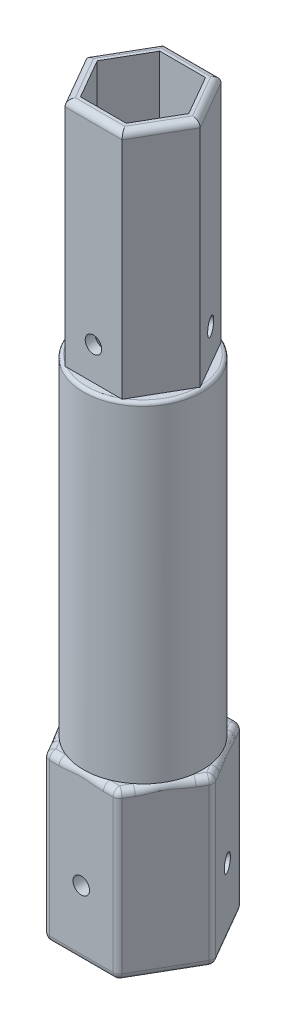
SolidWorks part; units mm, degrees
ref_plane "Front Plane" through (0, 0, 0) normal (0, 0, 1) x (1, 0, 0)
ref_plane "Top Plane" through (0, 0, 0) normal (0, 1, 0) x (1, 0, 0)
ref_plane "Right Plane" through (0, 0, 0) normal (1, 0, 0) x (0, 0, -1)
sketch "Sketch1" plane through (0, 0, 0) normal (0, 1, 0) x (1, 0, 0)
  line L1 (10.7965, 0) -> (5.3982, 9.35)
  line L2 (5.3982, 9.35) -> (-5.3982, 9.35)
  line L3 (-5.3982, 9.35) -> (-10.7965, 0)
  line L4 (-10.7965, 0) -> (-5.3982, -9.35)
  line L5 (-5.3982, -9.35) -> (5.3982, -9.35)
  line L6 (5.3982, -9.35) -> (10.7965, 0)
  circle A0 centre (0, 0) radius 9.35 construction
  dimension "D1" = 18.7
extrude "Base" add sketch "Sketch1" along normal blind 25 contours L6 L1 L2 L3 L4 L5
sketch "Sketch2" plane through (0, 25, 0) normal (0, 1, 0) x (1, 0, 0)
  circle A0 centre (0, 0) radius 9
  dimension "D1" = 18
extrude "Shaft" add sketch "Sketch2" along normal blind 50
sketch "Sketch3" plane through (0, 75, 0) normal (0, 1, 0) x (1, 0, 0)
  line L1 (8.6603, 0) -> (4.3301, 7.5)
  line L2 (4.3301, 7.5) -> (-4.3301, 7.5)
  line L3 (-4.3301, 7.5) -> (-8.6603, 0)
  line L4 (-8.6603, 0) -> (-4.3301, -7.5)
  line L5 (-4.3301, -7.5) -> (4.3301, -7.5)
  line L6 (4.3301, -7.5) -> (8.6603, 0)
  circle A0 centre (0, 0) radius 7.5 construction
  point P10 (0, 0)
  dimension "D1" = 15
extrude "MicMount" add sketch "Sketch3" along normal blind 35
sketch "Sketch4" plane through (0, 0, 0) normal (0, -1, 0) x (1, 0, 0)
  line L0 (5.3982, -9.35) -> (-5.3982, -9.35) construction
  line L1 (-3.6662, -6.35) -> (3.6662, -6.35)
  line L2 (3.6662, -6.35) -> (7.3323, 0)
  line L3 (7.3323, 0) -> (3.6662, 6.35)
  line L4 (3.6662, 6.35) -> (-3.6662, 6.35)
  line L5 (-3.6662, 6.35) -> (-7.3323, 0)
  line L6 (-7.3323, 0) -> (-3.6662, -6.35)
  circle A0 centre (0, 0) radius 6.35 construction
  dimension "D1" = 12.7
extrude "Cut-Extrude1" cut sketch "Sketch4" against normal up to surface (75 mm away) up to face at (0, 75, 0)
sketch "ScrewHoleLoc" plane through (6.4952, 0, -3.75) normal (0.866, 0, -0.5) x (-0.5, 0, -0.866)
  line L0 (0, 48.1931) -> (0, 111.8069) construction
  line L1 (9, 75) -> (-9, 75) construction
  point P0 (0, 80)
hole_wizard "ScrewHole" positions "3DSketch1" profile "Sketch6" hole size "Ø2.5" standard "ANSI Metric"
sketch3d "3DSketch1"
  point P0 (6.4952, 80, -3.75)
sketch "Sketch6" plane through (6.4952, 80, -3.75) normal (0, 1, 0) x (-0.5, 0, -0.866)
  line L0 (0, 0) -> (0, 2.7511)
  line L1 (0, 2.7511) -> (1.25, 2)
  line L2 (1.25, 2) -> (1.25, 0)
  line L5 (1.25, 0) -> (0, 0)
  line L10 (0, 2.7511) -> (-1.25, 2) construction
  line L11 (0, -6.35) -> (0, 107.95) construction
  dimension "Hole Dia." = 2.5
  dimension "Hole Depth" = 2
  dimension "Drill Angle" = 118
ref_axis "Axis1" through (0, 54.4687, 0) along (0, 1, 0)
pattern_circular "ScrewHoleS" count 3 over 360 about axis through (0, 54.4687, 0) along (0, 1, 0) of "ScrewHole"
sketch "Sketch7" plane through (0, 110, 0) normal (0, 1, 0) x (1, 0, 0)
  line L12 (3.4641, -6) -> (6.9282, 0)
  line L13 (6.9282, 0) -> (3.4641, 6)
  line L14 (3.4641, 6) -> (-3.4641, 6)
  line L15 (-3.4641, 6) -> (-6.9282, 0)
  line L16 (-6.9282, 0) -> (-3.4641, -6)
  line L17 (-3.4641, -6) -> (3.4641, -6)
  line L18 (3.4641, -6) -> (6.9282, 0)
  line L19 (6.9282, 0) -> (3.4641, 6)
  line L20 (3.4641, 6) -> (-3.4641, 6)
  line L21 (-3.4641, 6) -> (-6.9282, 0)
  line L22 (-6.9282, 0) -> (-3.4641, -6)
  line L23 (-3.4641, -6) -> (3.4641, -6)
  dimension "D1" = 1.5
extrude "Cut-Extrude2" cut sketch "Sketch7" against normal up to next
sketch "ShaftMountLoc" plane through (-8.0973, 0, -4.675) normal (-0.866, 0, -0.5) x (-0.5, 0, 0.866)
  line L0 (0, 10) -> (0, 7.4851) construction
  line L1 (5.3982, 25) -> (5.3982, 0) construction
  line L2 (-5.3982, 25) -> (-5.3982, 0) construction
  line L3 (-5.3982, 0) -> (5.3982, 0) construction
  point P0 (0, 10)
  dimension "D1" = 10
hole_wizard "ShaftMount" positions "3DSketch3" profile "Sketch10" hole size "Ø2.5" standard "ANSI Metric"
sketch3d "3DSketch3"
  point P0 (-8.0973, 10, -4.675)
sketch "Sketch10" plane through (-8.0973, 10, -4.675) normal (0, 1, 0) x (-0.5, 0, 0.866)
  line L0 (0, 0) -> (0, 18.7)
  line L1 (0, 18.7) -> (1.25, 18.7)
  line L2 (1.25, 18.7) -> (1.25, 0)
  line L5 (1.25, 0) -> (0, 0)
  line L11 (0, -6.35) -> (0, 107.95) construction
  dimension "Thru Hole Dia." = 2.5
  dimension "Thru Hole Depth" = 18.7
pattern_circular "CirPattern2" count 3 over 360 about axis through (0, 54.4687, 0) along (0, 1, 0) of "ShaftMount"
fillet "Fillet2" radius 1 24 edges at (8.0973, 0, -4.675) (-8.0973, 0, -4.675) (0, 0, 9.35) (5.4993, 0, 3.175) (0, 0, 6.35) (-5.4993, 0, 3.175) (-5.4993, 0, -3.175) (0, 0, -6.35) (5.4993, 0, -3.175) (5.3982, 12.5, 9.35) (8.0973, 25, 4.675) (10.7965, 12.5, 0) (8.0973, 0, 4.675) (-10.7965, 12.5, 0) (-8.0973, 25, 4.675) (-5.3982, 12.5, 9.35) (-8.0973, 0, 4.675) (5.3982, 12.5, -9.35) (0, 25, -9.35) (-5.3982, 12.5, -9.35) (0, 0, -9.35) (-8.0973, 25, -4.675) (8.0973, 25, -4.675) (0, 25, 9.35)
fillet "Fillet5" radius 1 6 edges at (6.4952, 110, -3.75) (6.4952, 110, 3.75) (0, 110, 7.5) (-6.4952, 110, 3.75) (-6.4952, 110, -3.75) (0, 110, -7.5)
fillet "Fillet8" radius 0.5 1 edges at (0, 75, 9)
equation "\"D1@Sketch3\"= \"SHAFT_MOUNTOD\""
equation "\"D1@Base\"=25"
equation "\"D1@Shaft\"=50"
equation "\"D1@Sketch2\"= \"SHAFT_D\""
equation "\"D1@Sketch4\" = \"SHAFT_BASEID\""
equation "\"D1@MicMount\" = \"SHAFT_MOUNTH\""
equation "\"D1@ShaftMountLoc\"= \"SHAFT_BASEHOLEH\""
equation "\"D1@Sketch1\" = \"SHAFT_BASEOD\""
equation "\"SHAFT_MOUNTOD\" = \"BMOUNT_HEXID\""
equation "\"CB_W\" = 5"
equation "\"CW_DEPTH\" = 1"
equation "\"PIN_SPACING\" = 2.54"
equation "\"PIN_D\" = 1"
equation "\"PCB_THICK\" = 1.5"
equation "\"TAP_HOLE\" = 2.5"
equation "\"SCREW_HOLE\" = 3"
equation "\"SLIPRING_D\" = 12.4"
equation "\"SLIPRING_MOUNTOD\" = 15"
equation "\"SLIPRING_MOUNTTHICK\" = 8"
equation "\"SLIPRING_MOUNT_LEGH\" = 12"
equation "\"PITCH_D\"= 44.45"
equation "\"HEX_D\"= 12.7"
equation "\"BODY_Y\"= 70"
equation "\"BODY_X\"= 60"
equation "\"BODY_Z\"= 120"
equation "\"BODY_THICK\"= 3"
equation "\"BODY_TOPTHICK\"= 4"
equation "\"STAND_R\" = 3"
equation "\"STAND_ZOFF\" = 10"
equation "\"STAND_XOFF\" = 5"
equation "\"MOTOR_ZOFF\" = 25"
equation "\"MOTOR_MOUNTANGLE\" = 120"
equation "\"MOTOR_D\"= 28"
equation "\"MOTOR_H\"= 19"
equation "\"MOTOR_HOLEDIST\"= 35"
equation "\"MOTOR_SHAFTOFF\" = 8"
equation "\"DRVR_Y\" = 31"
equation "\"DRVR_Z\" = 27"
equation "\"DRVR_YOFF\" = 15"
equation "\"DRVR_ARDOFF\" = 10"
equation "\"BEARING_OD\" = 28.575"
equation "\"BEARING_ID\" = 12.7"
equation "\"BEARING_THICK\" = 7.925"
equation "\"BEARING_FLANGE_D\" = 31.242"
equation "\"BEARING_FLANGETHICK\" = 1.575"
equation "\"COLLAR_OD\" = 20.5"
equation "\"BMOUNT_X\" = 30"
equation "\"BMOUNT_HEXID\" = 15"
equation "\"BMOUNT_HEXTHICK\" = 2"
equation "\"BMOUNT_HEXH\" = 35"
equation "\"BMOUNT_HOLEX\" = 4*\"PIN_SPACING\""
equation "\"BMOUNT_HOLEZ\" = 4*\"PIN_SPACING\""
equation "\"BMOUNT_SCREWH\" = 5"
equation "\"MBOARD_MHOLEX\" = 10*\"PIN_SPACING\""
equation "\"MBOARD_MHOLEXOFF\" = 2*\"PIN_SPACING\""
equation "\"MBOARD_MHOLEZ\" = 9*\"PIN_SPACING\""
equation "\"MBOARD_POGOSPACING\" = 1*\"PIN_SPACING\""
equation "\"MBOARD_POGOX\" = 7*\"PIN_SPACING\""
equation "\"MBOARD_POGOXOFF\" = 1*\"PIN_SPACING\""
equation "\"MBOARD_POGOZ\" = 7*\"PIN_SPACING\""
equation "\"MBOARD_W\" = 28*\"PIN_SPACING\""
equation "\"SHAFT_BASEID\" = 12.7"
equation "\"SHAFT_BASEOD\" = \"SHAFT_BASEID\" + 2*3"
equation "\"SHAFT_D\" = 18"
equation "\"HEXSHAFT_D\" = 12.75"
equation "\"HEXSHAFT_FILLET\" = 2.5"
equation "\"D1@ScrewHoleLoc\"=\"BMOUNT_SCREWH\""
equation "\"SHAFT_BASEHOLEH\" = 10"
equation "\"SHAFT_MOUNTH\" = \"BMOUNT_HEXH\" "
equation "\"MBOARD_MDEPTH\"= 15"
equation "\"STAND_XOFF\"= 5"
